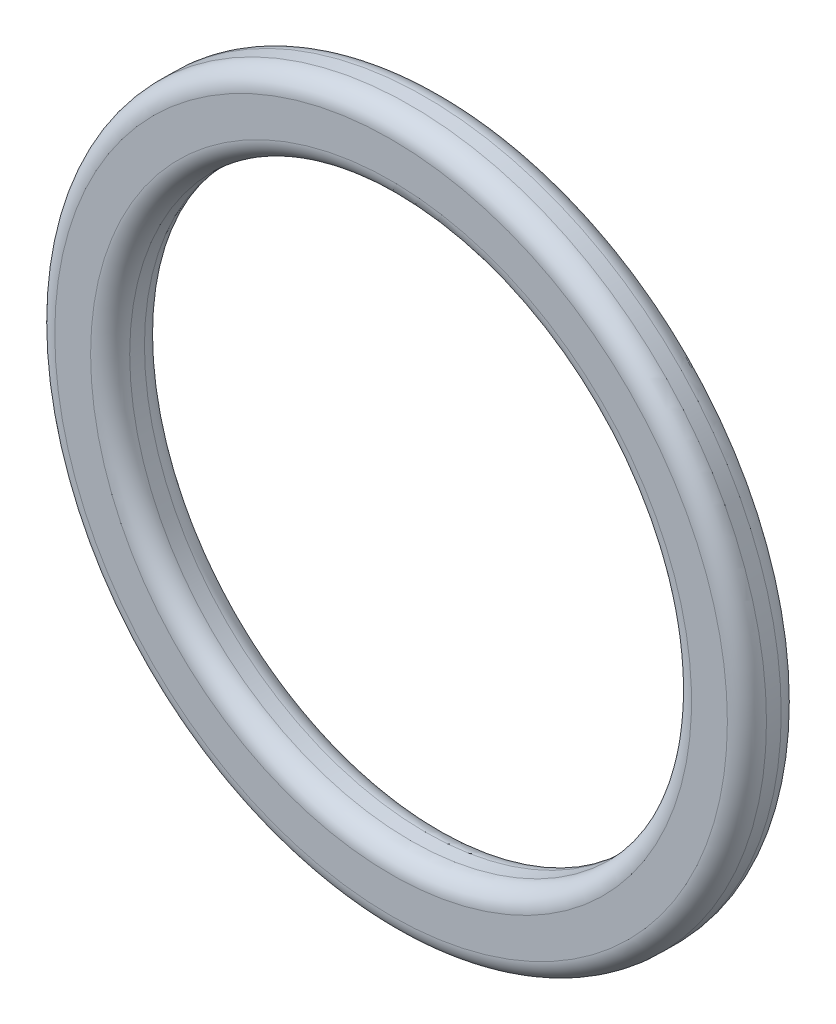
SolidWorks part; units mm, degrees
material "Rubber"
ref_plane "Front" through (0, 0, 0) normal (0, 0, 1) x (1, 0, 0)
ref_plane "Top" through (0, 0, 0) normal (0, 1, 0) x (1, 0, 0)
ref_plane "Right" through (0, 0, 0) normal (1, 0, 0) x (0, 0, -1)
ref_axis "Axis1" through (-84.4107, 0, 0) along (1, 0, 0)
ref_axis "Axis2" through (0, 64.3378, 0) along (0, -1, 0)
ref_axis "Axis3" through (0, 0, -102.329) along (0, 0, 1)
sketch "Sketch1" plane through (0, 0, 0) normal (1, 0, 0) x (0, 0, -1)
  line L0 (0, 0) -> (-4.0654, 0) construction
  line L2 (-1.465, 12) -> (-0.835, 12)
  line L3 (-2.3, 12.835) -> (-2.3, 14.365)
  line L4 (-1.465, 15.2) -> (-0.835, 15.2)
  line L5 (0, 12.835) -> (0, 14.365)
  arc A1 (-1.465, 12) -> (-2.3, 12.835) centre (-1.465, 12.835) cw
  arc A2 (-0.835, 12) -> (0, 12.835) centre (-0.835, 12.835) ccw
  arc A3 (-0.835, 15.2) -> (0, 14.365) centre (-0.835, 14.365) cw
  arc A4 (-2.3, 14.365) -> (-1.465, 15.2) centre (-1.465, 14.365) cw
  point P11 (-2.3, 12)
  point P16 (0, 15.2)
  point P19 (-2.3, 15.2)
  dimension "D6" = 0.835
  dimension "D3" = 12
  dimension "D4" = 2.3
  dimension "D5" = 3.2
revolve "Muokkautunut" add sketch "Sketch1" angle 360 about L0
sketch "Sketch2" plane through (0, 0, 0) normal (1, 0, 0) x (0, 0, -1)
  line L0 (1.8852, 0) -> (-2.1801, 0) construction
  circle A0 centre (-1.5, 13) radius 1.5
  dimension "D2" = 11.5
  dimension "D1" = 3
  dimension "D3" = 1.5
revolve "Muokkautumaton" [suppressed] add sketch "Sketch2" angle 360 about L0
equation "\"D3@Sketch2\" = \"D1@Sketch2\"/2"
